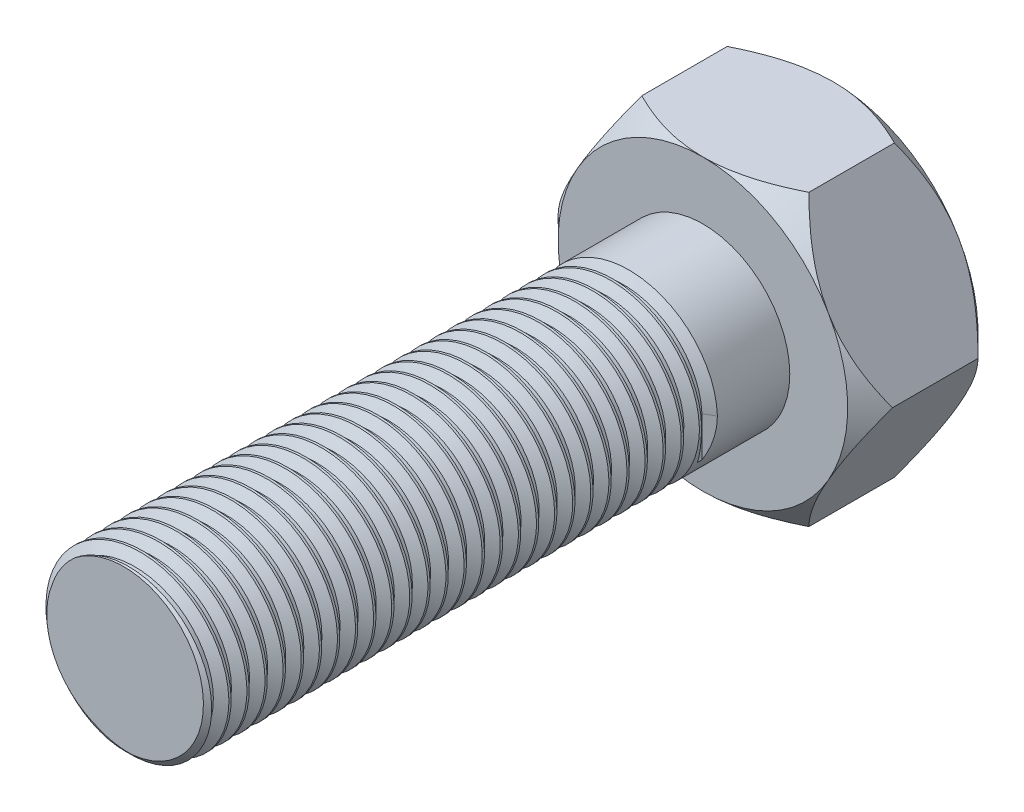
SolidWorks part; units mm, degrees
ref_plane "Front Plane" through (0, 0, 0) normal (0, 0, 1) x (1, 0, 0)
ref_plane "Top Plane" through (0, 0, 0) normal (0, 1, 0) x (1, 0, 0)
ref_plane "Right Plane" through (0, 0, 0) normal (1, 0, 0) x (0, 0, -1)
sketch "Sketch1" plane through (0, 0, 0) normal (0, 0, 1) x (1, 0, 0)
  line L1 (11.547, 0) -> (5.7735, 10)
  line L2 (5.7735, 10) -> (-5.7735, 10)
  line L3 (-5.7735, 10) -> (-11.547, 0)
  line L4 (-11.547, 0) -> (-5.7735, -10)
  line L5 (-5.7735, -10) -> (5.7735, -10)
  line L6 (5.7735, -10) -> (11.547, 0)
  circle A0 centre (0, 0) radius 10 construction
  dimension "D1" = 20
extrude "Boss-Extrude1" add sketch "Sketch1" along normal mid plane 9
sketch "Sketch2" plane through (0, 0, 4.5) normal (0, 0, 1) x (1, 0, 0)
  line L0 (-5.7735, 10) -> (-11.547, 0) construction
  circle A0 centre (0, 0) radius 10
extrude "Cut-Extrude1" cut sketch "Sketch2" against normal through all draft 45 flip side to cut
mirror "Mirror1" about plane through (0, 0, 0) normal (0, 0, 1) of "Cut-Extrude1"
sketch "Sketch3" plane through (0, 0, 4.5) normal (0, 0, 1) x (1, 0, 0)
  circle A0 centre (0, 0) radius 6
  dimension "D1" = 12
extrude "Boss-Extrude2" add sketch "Sketch3" along normal blind 40
chamfer "Chamfer1" distance 0.5 angle 45 1 edges at (6, 0, 44.5)
thread "Thread1" pitch 1.25 method cut profile "Thread Profile1" start angle 0, offset 5, length 0, pitch 1.25, diameter 12
ref_plane "Plane1" through (6, 0, 9.5) normal (0, -1, 0) x (1, 0, 0)
sketch "Thread Profile1" plane through (6, 0, 9.5) normal (0, -1, 0) x (1, 0, 0)
  line L0 (0, 0) -> (0, 1.25) construction
  line L11 (0, 0) -> (0, 1.0937)
  line L12 (0, 1.0937) -> (-0.6766, 0.7031)
  line L13 (-0.6766, 0.7031) -> (-0.6766, 0.3906)
  line L15 (-0.6766, 0.3906) -> (0, 0)
  line L17 (-0.6766, 0.5469) -> (0, 0.5469) construction
  point P2 (0, 0)
  dimension "Pitch" = 1.25
  dimension "Profile_Angle" = 60
  dimension "Profile_Land" = 0.3125
  dimension "Profile_Height" = 0.6766
sketch "Sketch11" plane through (0, 0, 0) normal (0, 1, 0) x (1, 0, 0)
  line L4 (6, -9.5) -> (5.3234, -9.8906)
  line L5 (5.3234, -9.8906) -> (5.3234, -10.2031)
  line L6 (5.3234, -10.2031) -> (6, -10.5937)
  line L7 (6, -10.5937) -> (6, -9.5)
  line L8 (6, -9.5) -> (5.3234, -9.8906)
  line L9 (5.3234, -9.8906) -> (5.3234, -10.2031)
  line L10 (5.3234, -10.2031) -> (6, -10.5937)
  line L11 (6, -10.5937) -> (6, -9.5)
  dimension "D1" = 0
extrude "Cut-Extrude2" cut sketch "Sketch11" against normal through all
